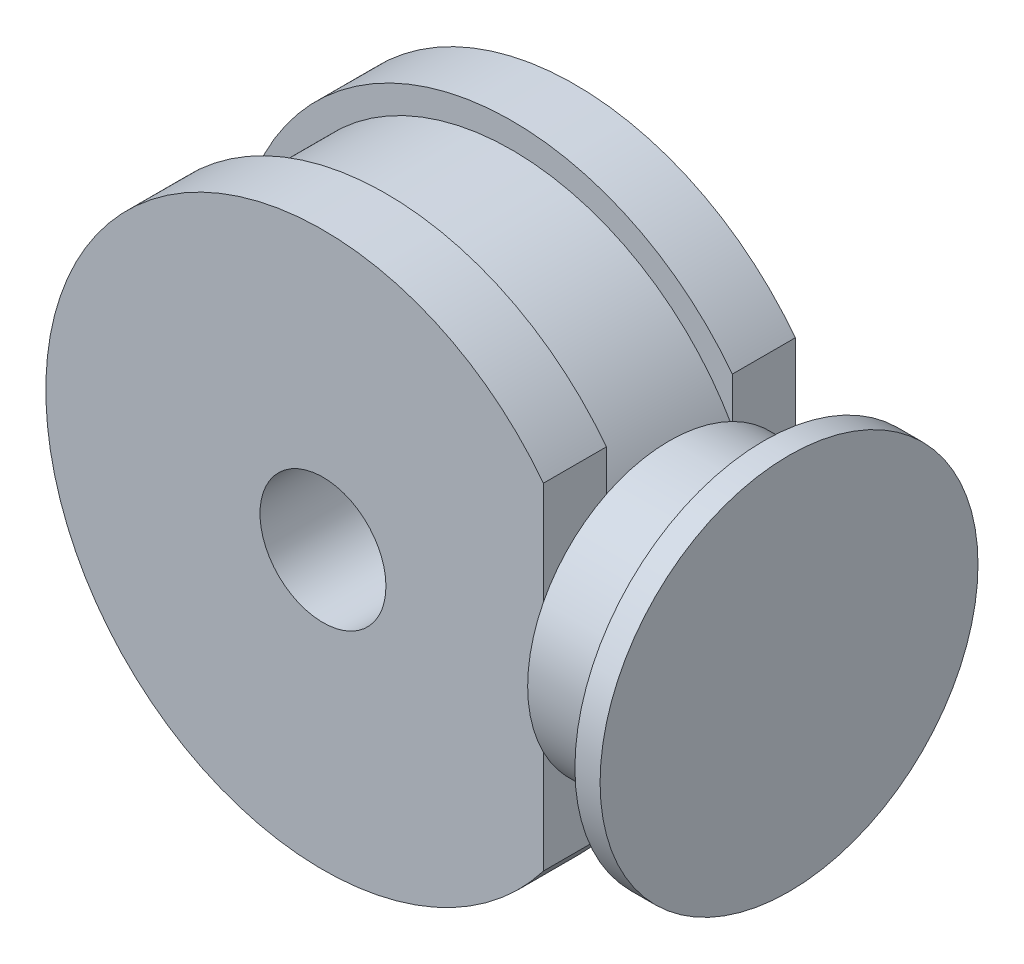
SolidWorks part; units mm, degrees
ref_plane "Plan de face" through (0, 0, 0) normal (0, 0, 1) x (1, 0, 0)
ref_plane "Plan de dessus" through (0, 0, 0) normal (0, 1, 0) x (1, 0, 0)
ref_plane "Plan de droite" through (0, 0, 0) normal (1, 0, 0) x (0, 0, -1)
sketch "Esquisse1" plane through (0, 0, 0) normal (0, 0, 1) x (1, 0, 0)
  circle A0 centre (0, 0) radius 44
  dimension "D1" = 88
extrude "Boss.-Extru.1" add sketch "Esquisse1" along normal blind 10
sketch "Esquisse2" plane through (0, 0, 10) normal (0, 0, 1) x (1, 0, 0)
  circle A0 centre (0, 0) radius 40
  dimension "D1" = 80
extrude "Boss.-Extru.2" add sketch "Esquisse2" along normal blind 20
sketch "Esquisse3" plane through (0, 0, 30) normal (0, 0, 1) x (1, 0, 0)
  circle A0 centre (0, 0) radius 44
extrude "Boss.-Extru.3" add sketch "Esquisse3" along normal blind 10
sketch "Esquisse5" plane through (0, 0, 40) normal (0, 0, 1) x (1, 0, 0)
  line L1 (35, 44.0697) -> (67.4724, 44.0697)
  line L2 (35, 44.0697) -> (35, -50.6619)
  line L3 (35, -50.6619) -> (67.4724, -50.6619)
  line L4 (67.4724, 44.0697) -> (67.4724, -50.6619)
  dimension "D1" = 35
extrude "Enlèv. mat.-Extru.2" cut sketch "Esquisse5" against normal through all
sketch "Esquisse4" plane through (0, 0, 40) normal (0, 0, 1) x (1, 0, 0)
  circle A0 centre (0, 0) radius 10
  dimension "D1" = 20
extrude "Enlèv. mat.-Extru.1" cut sketch "Esquisse4" against normal through all
ref_point "Point1"
sketch "Sketch1" plane through (35, 0, 0) normal (1, 0, 0) x (0, 0, -1)
  circle A0 centre (-20, 0) radius 22.5
extrude "Boss-Extrude1" add sketch "Sketch1" along normal blind 15
sketch "Sketch2" plane through (50, 0, 0) normal (1, 0, 0) x (0, 0, -1)
  circle A0 centre (-20, 0) radius 30
  dimension "D1" = 60
extrude "Boss-Extrude2" add sketch "Sketch2" along normal blind 4
